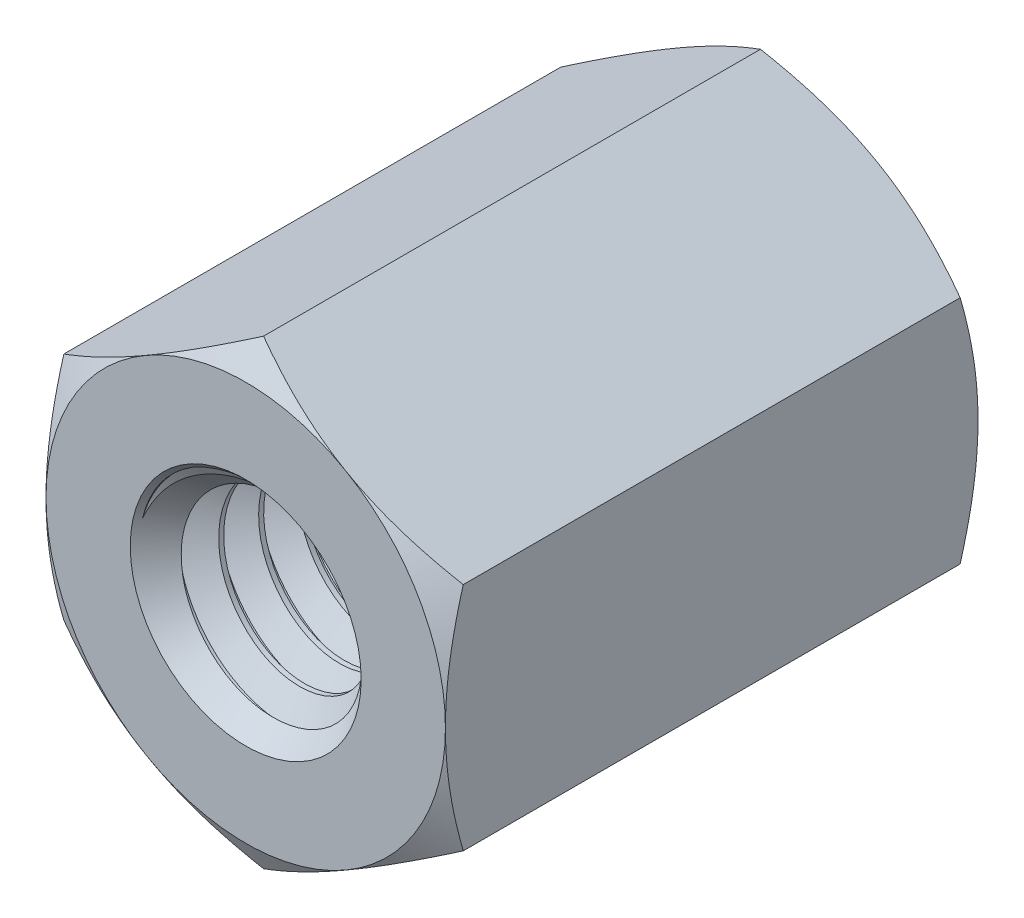
SolidWorks part; units mm, degrees
material "Stainless Steel 304"
ref_plane "Front Plane" through (0, 0, 0) normal (0, 0, 1) x (1, 0, 0)
ref_plane "Top Plane" through (0, 0, 0) normal (0, 1, 0) x (1, 0, 0)
ref_plane "Right Plane" through (0, 0, 0) normal (1, 0, 0) x (0, 0, -1)
sketch "Sketch3" plane through (0, 0, 0) normal (1, 0, 0) x (0, 0, -1)
  line L0 (-3, 0) -> (3, 0) construction
  line L1 (0, 2.25) -> (0, -2.25) construction
  line L2 (-3, 1.25) -> (-3, -1.25) construction
  point P2 (-1.8, 0)
  point P3 (1.8, 0)
  dimension "Length" = 6
  dimension "Min Thread Length" = 4.8
  dimension "D1" = 4.8
  dimension "Thread Dia" = 2.5
  dimension "Hex" = 4.5
sketch "Sketch1" plane through (0, 0, 0) normal (0, 0, 1) x (1, 0, 0)
  line L1 (0, 2.5981) -> (-2.25, 1.299)
  line L2 (-2.25, 1.299) -> (-2.25, -1.299)
  line L3 (-2.25, -1.299) -> (0, -2.5981)
  line L4 (0, -2.5981) -> (2.25, -1.299)
  line L5 (2.25, -1.299) -> (2.25, 1.299)
  line L6 (2.25, 1.299) -> (0, 2.5981)
  circle A0 centre (0, 0) radius 2.25 construction
  circle A1 centre (0, 0) radius 1.25
extrude "Extrude1" add sketch "Sketch1" along normal up to vertex (3 mm away) and the other way up to vertex (3 mm away) up to point (0, 0, 3) other way up to point (0, 0, -3)
sketch "Sketch11" plane through (0, 0, -3) normal (0, 0, -1) x (-1, 0, 0)
  circle A0 centre (0, 0) radius 1.25 construction
  circle A1 centre (0, 0) radius 1.25
curve "Helix/Spiral1" pitch 0.45 height 6.45 radius 1.25 centre (0, 0, -3) axis (0, 0, 1) start towards (0, 1, 0) parameters "Pitch"=0.45
sketch "Sketch12" plane through (0, 0, 0) normal (1, 0, 0) x (0, 0, -1)
  line L0 (3.3938, 1.25) -> (3, 1.25)
  line L1 (3.3938, 1.25) -> (3.225, 0.9577)
  line L2 (3.225, 0.9577) -> (3.1688, 0.9577)
  line L3 (3.1688, 0.9577) -> (3, 1.25)
  line L4 (3.1969, 0.9577) -> (3.1969, 1.25) construction
  line L5 (3.3094, 1.1039) -> (3.0844, 1.1039) construction
  dimension "D1" = 0.0563
  dimension "D2" = 0.225
  dimension "D3" = 60
sweep "Sweep1" add profiles "Sketch12" path "Helix/Spiral1"
sketch "Sketch6" plane through (0, 0, -3) normal (0, 0, -1) x (-1, 0, 0)
  line L6 (0, 2.5981) -> (-2.25, 1.299)
  line L7 (-2.25, 1.299) -> (-2.25, -1.299)
  line L8 (-2.25, -1.299) -> (0, -2.5981)
  line L9 (0, -2.5981) -> (2.25, -1.299)
  line L10 (2.25, -1.299) -> (2.25, 1.299)
  line L11 (2.25, 1.299) -> (0, 2.5981)
  line L12 (0, 2.5981) -> (-2.25, 1.299)
  line L13 (-2.25, 1.299) -> (-2.25, -1.299)
  line L14 (-2.25, -1.299) -> (0, -2.5981)
  line L15 (0, -2.5981) -> (2.25, -1.299)
  line L16 (2.25, -1.299) -> (2.25, 1.299)
  line L17 (2.25, 1.299) -> (0, 2.5981)
  dimension "D1" = 0
extrude "Extrude2" cut sketch "Sketch6" along normal through all
sketch "Sketch7" plane through (0, 0, -3) normal (0, 0, -1) x (-1, 0, 0)
  circle A2 centre (0, 0) radius 1.3008
  circle A3 centre (0, 0) radius 1.3008
  dimension "D1" = 0.0508
extrude "Extrude3" cut sketch "Sketch7" against normal through all draft 43
sketch "Sketch8" plane through (0, 0, -3) normal (0, 0, -1) x (-1, 0, 0)
  circle A0 centre (0, 0) radius 2.25 construction
  circle A1 centre (0, 0) radius 2.25
extrude "Extrude4" cut sketch "Sketch8" against normal through all draft 60 flip side to cut
mirror "Mirror1" about plane through (0, 0, 0) normal (0, 0, 1) of "Extrude2", "Extrude3", "Extrude4"
sketch "Sketch9" [suppressed] plane through (0, 0, 0) normal (1, 0, 0) x (0, 0, -1)
  line L1 (-1.2, 1.1353) -> (1.2, 1.1353)
  line L2 (-1.2, 1.1353) -> (-1.2, 0)
  line L3 (-1.2, 0) -> (1.2, 0)
  line L4 (1.2, 1.1353) -> (1.2, 0)
  line L7 (-6, 0) -> (6, 0) construction
revolve "Revolve" [suppressed] add sketch "Sketch9" angle 360 about L0
sketch "Sketch10" [suppressed] plane through (0, 0, 0) normal (1, 0, 0) x (0, 0, -1)
  line L0 (6, 1.25) -> (1.2, 1.25)
  line L1 (-6, 1.25) -> (-1.2, 1.25)
  line L2 (1.2, 1.25) -> (1.2, -1.25)
  line L3 (-6, -1.25) -> (-1.2, -1.25)
  line L4 (-1.2, 1.25) -> (-1.2, -1.25)
  line L5 (1.2, -1.25) -> (6, -1.25)
equation "\"D1@Sketch3\" = \"Min Thread Length@Sketch3\""
equation "\"D3@Helix/Spiral1\" = \"Length@Sketch3\"+\"Pitch@Helix/Spiral1\""
equation "\"D1@Sketch12\" = \"Pitch@Helix/Spiral1\"*.125"
equation "\"D2@Sketch12\" = \"Pitch@Helix/Spiral1\"*.5"
